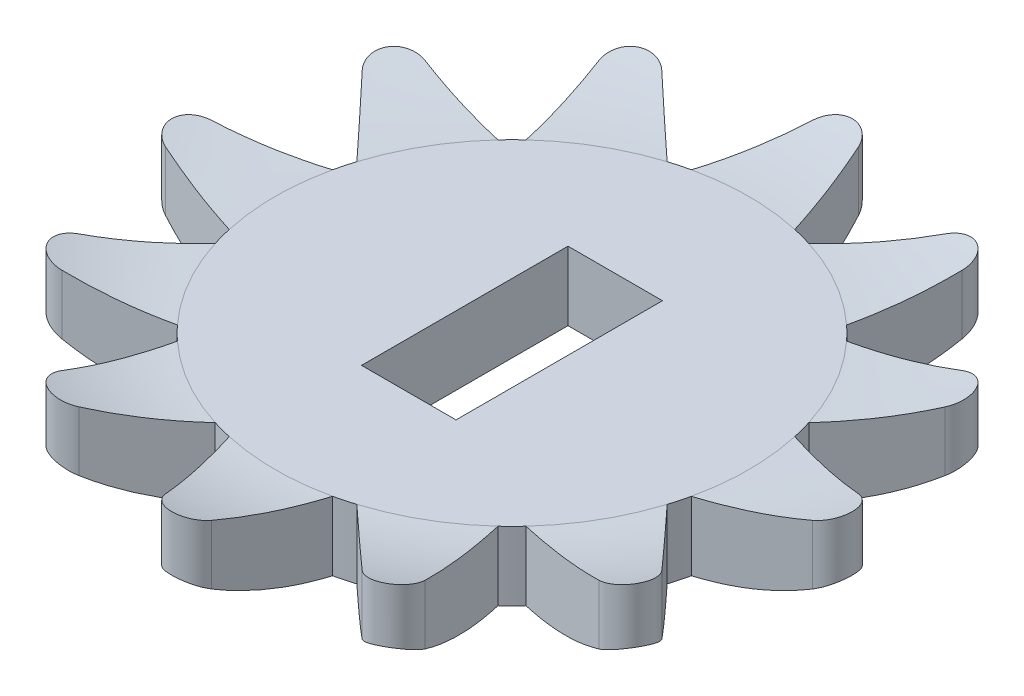
SolidWorks part; units mm, degrees
material "1060 Alloy"
ref_plane "Front Plane" through (0, 0, 0) normal (0, 0, 1) x (1, 0, 0)
ref_plane "Top Plane" through (0, 0, 0) normal (0, 1, 0) x (1, 0, 0)
ref_plane "Right Plane" through (0, 0, 0) normal (1, 0, 0) x (0, 0, -1)
sketch "Sketch1" plane through (0, 0, 0) normal (0, 1, 0) x (1, 0, 0)
  line L2 (0, 9.18) -> (0, 4.2387) construction
  line L6 (1.5, 6.7094) -> (0.6685, 9.3876)
  line L7 (-1.5, 6.7094) -> (-0.6685, 9.3876)
  line L8 (2.0556, 6.5605) -> (4.1148, 8.4641)
  line L9 (4.6537, 5.0605) -> (5.2727, 7.7956)
  line L11 (5.0605, 4.6537) -> (7.7956, 5.2727)
  line L12 (6.5605, 2.0556) -> (8.4641, 4.1148)
  line L14 (6.7094, 1.5) -> (9.3876, 0.6685)
  line L15 (6.7094, -1.5) -> (9.3876, -0.6685)
  line L17 (6.5605, -2.0556) -> (8.4641, -4.1148)
  line L18 (5.0605, -4.6537) -> (7.7956, -5.2727)
  line L20 (4.6537, -5.0605) -> (5.2727, -7.7956)
  line L21 (2.0556, -6.5605) -> (4.1148, -8.4641)
  line L23 (1.5, -6.7094) -> (0.6685, -9.3876)
  line L24 (-1.5, -6.7094) -> (-0.6685, -9.3876)
  line L26 (-2.0556, -6.5605) -> (-4.1148, -8.4641)
  line L27 (-4.6537, -5.0605) -> (-5.2727, -7.7956)
  line L29 (-5.0605, -4.6537) -> (-7.7956, -5.2727)
  line L30 (-6.5605, -2.0556) -> (-8.4641, -4.1148)
  line L32 (-6.7094, -1.5) -> (-9.3876, -0.6685)
  line L33 (-6.7094, 1.5) -> (-9.3876, 0.6685)
  line L35 (-6.5605, 2.0556) -> (-8.4641, 4.1148)
  line L36 (-5.0605, 4.6537) -> (-7.7956, 5.2727)
  line L38 (-4.6537, 5.0605) -> (-5.2727, 7.7956)
  line L39 (-2.0556, 6.5605) -> (-4.1148, 8.4641)
  line L40 (0, 0) -> (0, 1.905) construction
  line L41 (0, 0) -> (-4.13, 0) construction
  line L42 (0, 0) -> (4.13, 0) construction
  arc A3 (-6.7094, -1.5) -> (-6.5605, -2.0556) centre (0, 0) ccw
  arc A4 (0.6685, 9.3876) -> (-0.6685, 9.3876) centre (0, 9.18) ccw
  arc A5 (5.2727, 7.7956) -> (4.1148, 8.4641) centre (4.59, 7.9501) ccw
  arc A6 (8.4641, 4.1148) -> (7.7956, 5.2727) centre (7.9501, 4.59) ccw
  arc A7 (9.3876, -0.6685) -> (9.3876, 0.6685) centre (9.18, 0) ccw
  arc A8 (7.7956, -5.2727) -> (8.4641, -4.1148) centre (7.9501, -4.59) ccw
  arc A9 (4.1148, -8.4641) -> (5.2727, -7.7956) centre (4.59, -7.9501) ccw
  arc A10 (-0.6685, -9.3876) -> (0.6685, -9.3876) centre (0, -9.18) ccw
  arc A11 (-5.2727, -7.7956) -> (-4.1148, -8.4641) centre (-4.59, -7.9501) ccw
  arc A12 (-8.4641, -4.1148) -> (-7.7956, -5.2727) centre (-7.9501, -4.59) ccw
  arc A13 (-9.3876, 0.6685) -> (-9.3876, -0.6685) centre (-9.18, 0) ccw
  arc A14 (-7.7956, 5.2727) -> (-8.4641, 4.1148) centre (-7.9501, 4.59) ccw
  arc A15 (-4.1148, 8.4641) -> (-5.2727, 7.7956) centre (-4.59, 7.9501) ccw
  arc A16 (-6.5605, 2.0556) -> (-6.7094, 1.5) centre (0, 0) ccw
  arc A17 (-4.6537, 5.0605) -> (-5.0605, 4.6537) centre (0, 0) ccw
  arc A18 (-1.5, 6.7094) -> (-2.0556, 6.5605) centre (0, 0) ccw
  arc A19 (2.0556, 6.5605) -> (1.5, 6.7094) centre (0, 0) ccw
  arc A20 (5.0605, 4.6537) -> (4.6537, 5.0605) centre (0, 0) ccw
  arc A21 (6.7094, 1.5) -> (6.5605, 2.0556) centre (0, 0) ccw
  arc A22 (6.5605, -2.0556) -> (6.7094, -1.5) centre (0, 0) ccw
  arc A23 (4.6537, -5.0605) -> (5.0605, -4.6537) centre (0, 0) ccw
  arc A24 (1.5, -6.7094) -> (2.0556, -6.5605) centre (0, 0) ccw
  arc A25 (-2.0556, -6.5605) -> (-1.5, -6.7094) centre (0, 0) ccw
  arc A26 (-5.0605, -4.6537) -> (-4.6537, -5.0605) centre (0, 0) ccw
  point P73 (0, 0)
  dimension "D3" = 13.75
  dimension "D5" = 1.4
  dimension "D4" = 3
  dimension "D6" = 12
extrude "Boss-Extrude1" add sketch "Sketch1" along normal blind 2.45
sketch "Sketch7" plane through (0, 0, 0) normal (0, 0, 1) x (1, 0, 0)
  line L0 (0, 2.45) -> (-6.875, 2.45)
  line L1 (0.6685, 2.45) -> (-0.6685, 2.45) construction
  line L2 (-7.7956, 2.45) -> (-5.0605, 2.45) construction
  line L3 (-6.875, 2.45) -> (-9.88, 2.45)
  line L4 (-6.875, 0) -> (-4.1148, 0)
  line L5 (-6.875, 2) -> (-6.875, 2.45)
  line L6 (-7.7956, 0) -> (-5.0605, 0) construction
  line L7 (-6.875, 2) -> (0, 2)
  line L8 (0, 2) -> (0, 2.45)
  line L9 (-6.875, 2.45) -> (-9.88, 2.45)
  line L10 (-9.88, 2.45) -> (-9.88, 0) construction
  line L11 (-6.875, 2) -> (-6.875, 0)
  line L12 (-9.88, 0.85) -> (-9.88, 0)
  line L13 (-9.88, 0) -> (-6.875, 0)
  line L14 (0, 0) -> (0, 4.3852) construction
  arc A0 (-6.875, 0) -> (-9.88, 0.85) centre (-6.875, 5.7368) cw
  arc A1 (-6.875, 2) -> (-9.88, 2.45) centre (-6.875, 12.2584) cw
  dimension "D1" = 6.875
  dimension "D2" = 2
  dimension "D3" = 1.6
revolve "Cut-Revolve2" cut sketch "Sketch7" angle 360 about L14 region at (-3.4375, 2.225, 0) region at (-9.1403, 0.2514, 0) region at (-8.0052, 2.2697, 0)
sketch "Sketch8" plane through (0, 2, 0) normal (0, 1, 0) x (1, 0, 0)
  line L1 (-1.3716, 2.9972) -> (1.3716, 2.9972)
  line L2 (-1.3716, 2.9972) -> (-1.3716, -2.9972)
  line L3 (-1.3716, -2.9972) -> (1.3716, -2.9972)
  line L4 (1.3716, 2.9972) -> (1.3716, -2.9972)
  point P4 (-1.3716, 0)
  point P6 (0, 2.9972)
  dimension "D1" = 2.7432
  dimension "D2" = 5.9944
extrude "Cut-Extrude1" cut sketch "Sketch8" against normal blind 10
